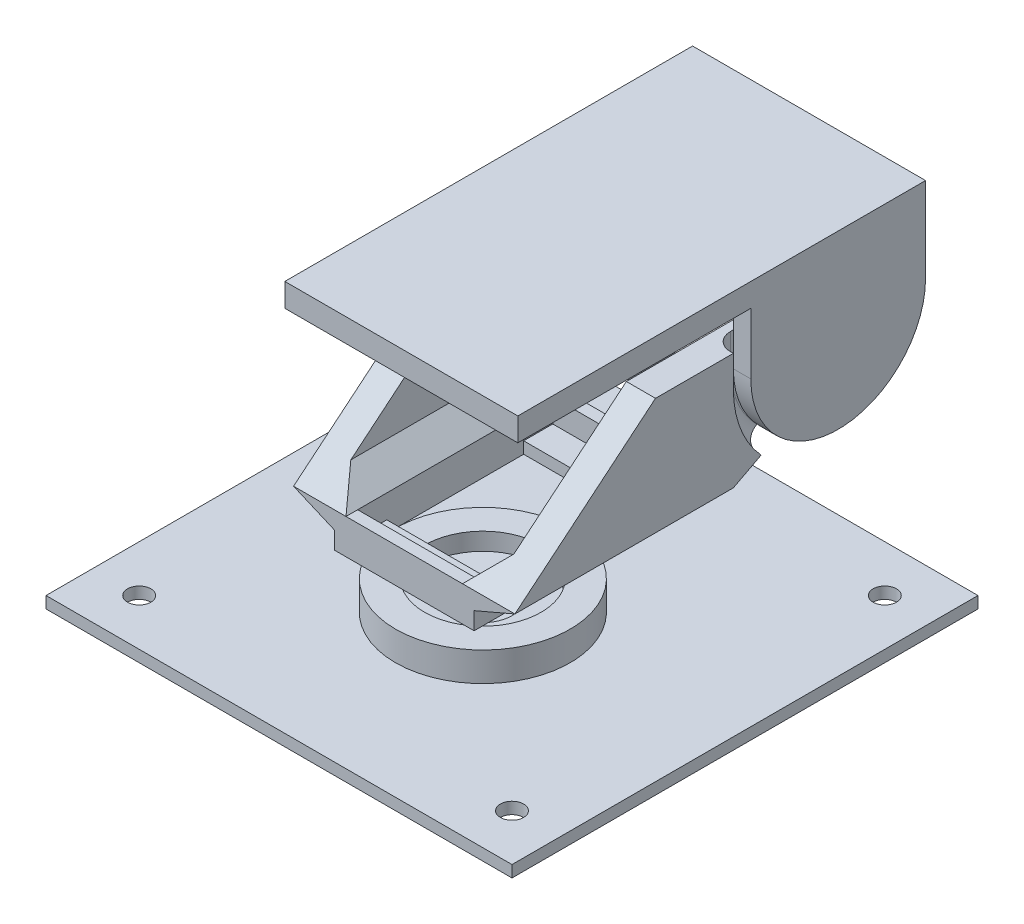
SolidWorks part; units mm, degrees
note: The reader was unsure of these and kept them because the rebuilt part matched: shared geometry of "Sketch9<3>".
other "TiltMount"
other "Base"
other "PanMount"
other "Pin_outer"
other "Pin_inner"
ref_plane "Front Plane" through (0, 0, 0) normal (0, 0, 1) x (1, 0, 0)
ref_plane "Top Plane" through (0, 0, 0) normal (0, 1, 0) x (1, 0, 0)
ref_plane "Right Plane" through (0, 0, 0) normal (1, 0, 0) x (0, 0, -1)
sketch "Sketch1" plane through (0, 0, 0) normal (0, 1, 0) x (1, 0, 0)
  line L1 (-40, -40) -> (40, -40)
  line L2 (-40, -40) -> (-40, 40)
  line L3 (-40, 40) -> (40, 40)
  line L4 (40, -40) -> (40, 40)
  line L5 (-40, -40) -> (40, 40) construction
  line L6 (-40, 40) -> (40, -40) construction
  point P0 (0, 0)
  dimension "D1" = 80
  dimension "D2" = 80
extrude "Boss-Extrude1" add sketch "Sketch1" along normal blind 2
sketch "Sketch2" plane through (0, 2, 0) normal (0, 1, 0) x (1, 0, 0)
  line L0 (0, 0) -> (0, -5) construction
  circle A0 centre (0, -5) radius 5
  circle A1 centre (0, -5) radius 15
  dimension "D1" = 10
  dimension "D3" = 30
  dimension "D2" = 5
extrude "Boss-Extrude2" add sketch "Sketch2" along normal blind 5
sketch "Sketch14" plane through (0, 2, 0) normal (0, 1, 0) x (1, 0, 0)
  line L8 (32, -32) -> (32, 32)
  line L9 (32, 32) -> (-32, 32)
  line L10 (-32, 32) -> (-32, -32)
  line L11 (-32, -32) -> (32, -32)
  line L12 (32, -32) -> (32, 32) construction
  line L13 (32, 32) -> (-32, 32) construction
  line L14 (-32, 32) -> (-32, -32) construction
  line L15 (-32, -32) -> (32, -32) construction
  circle A0 centre (-32, 32) radius 2
  circle A1 centre (32, 32) radius 2
  circle A2 centre (32, -32) radius 2
  circle A3 centre (-32, -32) radius 2
  dimension "D2" = 4
  dimension "D1" = 8
sketch "Sketch13" plane through (0, 7, 0) normal (0, 1, 0) x (1, 0, 0)
  circle A0 centre (0, -5) radius 10
  dimension "D1" = 20
extrude "Cut-Extrude1" cut sketch "Sketch13" against normal offset from surface (3 mm away) 2 up to face at (0, 2, 20)
sketch "Sketch4" plane through (0, 2, 0) normal (0, 1, 0) x (1, 0, 0)
  line L0 (0, 0) -> (0, 17) construction
  line L1 (-12, 19) -> (12, 19)
  line L2 (-12, 19) -> (-12, -18.5)
  line L3 (-12, -18.5) -> (12, -18.5)
  line L4 (12, 19) -> (12, -18.5)
  line L5 (-10, 17) -> (-10, -16.5)
  line L6 (-10, -16.5) -> (10, -16.5)
  line L7 (10, 17) -> (10, -16.5)
  line L8 (-10, 17) -> (10, 17)
  dimension "D1" = 33.5
  dimension "D2" = 24
  dimension "D3" = 17
  dimension "D4" = 2
extrude "Boss-Extrude3" add sketch "Sketch4" along normal blind 6 from offset 10
sketch "Sketch5" plane through (-12, 0, 0) normal (-1, 0, 0) x (0, 0, 1)
  line L0 (-42, 38) -> (-5.6333, 38)
  line L1 (-5.6333, 38) -> (18.5, 18)
  line L2 (18.5, 18) -> (-19, 18)
  line L3 (-19, 18) -> (-42, 30)
  line L6 (-42, 30) -> (-42, 38)
  line L7 (-42, 32.6957) -> (-37, 32.6957) construction
  line L8 (-37, 32.6957) -> (-37, 38) construction
  line L9 (-37, 32.6957) -> (-37, 27.3913) construction
  line L15 (-19, 18) -> (-19, 12) construction
  circle A0 centre (-37, 32.6957) radius 1.3
  dimension "D2" = 2.6
  dimension "D1" = 20
  dimension "D3" = 8
  dimension "D4" = 5
  dimension "D5" = 18
extrude "Boss-Extrude4" add sketch "Sketch5" along normal blind 5 from offset 2 separate body
sketch "Sketch6" plane through (0, 0, 18.5) normal (0, 0, 1) x (1, 0, 0)
  line L0 (-19, 18) -> (-12, 15)
  line L1 (-12, 18) -> (-12, 12) construction
  line L2 (-12, 15) -> (-12, 18)
  line L3 (-14, 18) -> (-19, 18)
  line L4 (-14, 22) -> (-10, 18)
  line L5 (-14, 18) -> (-14, 38) construction
  line L6 (-12, 18) -> (12, 18) construction
  line L7 (-10, 18) -> (-12, 18)
  line L8 (-14, 18) -> (-14, 22)
  dimension "D1" = 4
extrude "Boss-Extrude5" add sketch "Sketch6" against normal up to surface (45.1667 mm away) up to face at (-16.5, 24, -30.5)
sketch "Sketch10" plane through (0, 12, 0) normal (0, -1, 0) x (1, 0, 0)
  line L0 (10, 16.5) -> (10, -17) construction
  line L1 (-10, 16.5) -> (10, 16.5)
  line L2 (-10, 16.5) -> (-10, 11.5)
  line L3 (-10, 11.5) -> (10, 11.5)
  line L4 (10, 16.5) -> (10, 11.5)
  line L5 (-10, -17) -> (-10, 16.5) construction
  line L6 (10, -17) -> (-10, -17)
  line L7 (10, -17) -> (10, -12)
  line L8 (10, -12) -> (-10, -12)
  line L9 (-10, -17) -> (-10, -12)
  dimension "D1" = 5
extrude "Boss-Extrude8" add sketch "Sketch10" against normal blind 2
sketch "Sketch20" plane through (-14, 0, 0) normal (-1, 0, 0) x (0, 0, 1)
  line L0 (18.5, 18) -> (13.6733, 22) construction
  line L1 (18.5, 18) -> (13.6733, 22)
  line L2 (13.6733, 22) -> (18.5, 22)
  line L3 (18.5, 22) -> (18.5, 18)
extrude "Cut-Extrude3" cut sketch "Sketch20" against normal blind 10
mirror "Mirror2" about plane through (0, 0, 0) normal (1, 0, 0) of bodies 131 105
sketch "Sketch9" plane through (-19, 0, 0) normal (1, 0, 0) x (0, 0, -1)
  line L0 (42, 43.1957) -> (38.9267, 32.1591)
  line L2 (32, 43.1957) -> (35.0733, 32.1591)
  line L3 (32, 43.1957) -> (42, 43.1957)
  line L4 (37, 32.6957) -> (37, 43.1957) construction
  arc A0 (35.0733, 32.1591) -> (38.9267, 32.1591) centre (37, 32.6957) ccw
  circle A1 centre (37, 32.6957) radius 1.3
  circle A3 centre (37, 32.6957) radius 1.3 construction
  point P16 (37, 43.1957)
  dimension "D1" = 2
  dimension "D2" = 10.5
  dimension "D3" = 10
extrude "Boss-Extrude7" add sketch "Sketch9" against normal blind 2 separate body
extrude "Cut-Extrude2" cut sketch "Sketch14" against normal blind 2
extrude "Boss-Extrude11" add sketch "Sketch9<3>" along normal blind 2 from offset 33 separate body
sketch "Sketch9<3>" plane through (-19, 0, 0) normal (1, 0, 0) x (0, 0, -1) same geometry as "Sketch9"
sketch "Sketch7" plane through (0, 38, 0) normal (0, 1, 0) x (1, 0, 0)
  line L0 (0, 0) -> (0, 1.5) construction
  line L1 (-21, 52) -> (19, 52)
  line L2 (-21, 52) -> (-21, -18)
  line L3 (-21, -18) -> (19, -18)
  line L4 (19, 52) -> (19, -18)
  line L6 (-21, 42) -> (-21, 32) construction
  line L7 (-19, 42) -> (-14, 42) construction
  line L8 (19, 5.6333) -> (19, 42) construction
  dimension "D1" = 10
  dimension "D3" = 70
extrude "Boss-Extrude6" add sketch "Sketch7" along normal blind 4 from surface at 5.1957 starting at face at (-20, 43.1957, -37)
sketch "Sketch12" plane through (-14, 0, 0) normal (1, 0, 0) x (0, 0, -1)
  line L3 (15.5, 26.6729) -> (20, 26.6729)
  line L5 (52, 43.1957) -> (-18, 43.1957) construction
  line L8 (48, 26.6729) -> (43.5, 26.6729)
  line L10 (48, 26.6729) -> (52, 43.1957)
  line L11 (52, 47.1957) -> (52, 43.1957) construction
  line L12 (52, 43.1957) -> (-18, 43.1957) construction
  line L13 (52, 43.1957) -> (47.5, 43.1957)
  line L14 (15.5, 26.6729) -> (11.5, 43.1957)
  line L15 (11.5, 43.1957) -> (16, 43.1957)
  line L17 (47.5, 43.1957) -> (43.5, 34.6957)
  line L18 (43.5, 34.6957) -> (43.5, 26.6729)
  line L19 (16, 43.1957) -> (20, 34.6957)
  line L20 (20, 34.6957) -> (20, 26.6729)
  point P6 (20.4457, 26.6729)
  point P9 (0, 0)
  dimension "D1" = 6.5
  dimension "D2" = 4.5
  dimension "D3" = 17
  dimension "D4" = 17
  dimension "D5" = 4.5
  dimension "D6" = 2
extrude "Boss-Extrude12" add sketch "Sketch12" against normal blind 3 from offset 22
ref_plane "Plane2" through (0, 39.9046, -11.1121) normal (0, 0.9633, -0.2683) x (1, 0, 0)
ref_plane "Plane1" through (0, 0, 0) normal (-1, 0, 0) x (0, -1, 0)
sketch "Sketch19" plane through (0, 39.9046, -11.1121) normal (0, 0.9633, -0.2683) x (1, 0, 0)
  line L0 (-21, 25.5729) -> (-21, 25.3729)
  line L1 (-21, 26.8729) -> (-21.5, 26.8729)
  line L2 (-21, 28.1729) -> (-21, 25.5729) construction
  line L3 (-21, 25.5729) -> (-14, 25.5729)
  line L4 (-21.5, 28.9194) -> (-21.5, 24.8264) construction
  line L5 (-14, 25.5729) -> (-14, 26.8729) construction
  line L6 (-14, 26.8729) -> (-21, 26.8729) construction
  line L7 (-21, 28.1729) -> (-21, 25.5729) construction
  line L8 (-14, 26.2229) -> (-20.5, 26.2229)
  line L9 (-20.5, 26.2229) -> (-20.5, 26.8729)
  line L10 (-20.5, 26.8729) -> (-21, 26.8729)
  line L11 (-14, 26.2229) -> (-14, 25.5729)
  line L12 (-14, 19.7875) -> (-14, -19.0739) construction
  line L13 (-21.5, 26.8729) -> (-21.5, 25.3729)
  line L14 (-21.5, 25.3729) -> (-21, 25.3729)
  point P8 (-21.5, 26.8729)
  dimension "D1" = 0.5
  dimension "D2" = 1.5
  dimension "D4" = 0.5
revolve "Revolve1" add sketch "Sketch19" angle 360 about L6
sketch "Sketch23" plane through (0, 39.9046, -11.1121) normal (0, 0.9633, -0.2683) x (1, 0, 0)
  line L0 (-20.5, 26.8729) -> (-14, 26.8729)
  line L1 (-21, 26.8729) -> (-19, 26.8729) construction
  line L3 (-14, -4.7671) -> (-14, 30.2667) construction
  line L4 (-13, 26.8729) -> (-13, 24.9826) construction
  line L5 (-20.5, 26.2229) -> (-20.5, 27.5229) construction
  line L6 (-14, 27.5229) -> (-14, 28.3729)
  line L7 (-20.5, 26.8729) -> (-20.5, 27.5229)
  line L8 (-21, 28.3729) -> (-14, 28.3729) construction
  line L9 (-14, 26.8729) -> (-13, 26.8729)
  line L10 (-20.5, 27.5229) -> (-14, 27.5229)
  line L11 (-14, 26.2229) -> (-14, 27.5229) construction
  line L12 (-13, 26.8729) -> (-13, 28.3729)
  line L13 (-13, 28.3729) -> (-14, 28.3729)
  line L14 (-21, -30.001) -> (-21, 37.4333) construction
  line L15 (-21, 28.3729) -> (-21.5, 28.3729) construction
  dimension "D1" = 1
revolve "Revolve2" add sketch "Sketch23" angle 360 about L0
delete or keep bodies "Body-Delete/Keep 2" type delete bodies bodies 122
sketch "Sketch25" plane through (19, 0, 0) normal (1, 0, 0) x (0, 0, -1)
  line L0 (22, 32.6957) -> (22, 43.1957)
  line L1 (52, 43.1957) -> (-18, 43.1957) construction
  line L2 (52, 32.6957) -> (52, 43.1957)
  line L3 (22, 43.1957) -> (52, 43.1957)
  arc A0 (22, 32.6957) -> (52, 32.6957) centre (37, 32.6957) ccw
  dimension "D1" = 15
extrude "Boss-Extrude13" add sketch "Sketch25" against normal blind 3
sketch "Sketch26" plane through (19, 0, 0) normal (1, 0, 0) x (0, 0, -1)
  line L10 (-21, 40.1957) -> (19, 40.1957)
  line L11 (19, 40.1957) -> (19, 32.6957)
  line L12 (55, 32.6957) -> (55, 50.1957)
  line L13 (55, 50.1957) -> (-21, 50.1957)
  line L14 (-21, 50.1957) -> (-21, 40.1957)
  line L15 (-21, 40.1957) -> (19, 40.1957)
  line L17 (55, 32.6957) -> (55, 50.1957)
  line L18 (55, 50.1957) -> (-21, 50.1957)
  line L19 (-21, 50.1957) -> (-21, 40.1957)
  line L20 (19, 40.1957) -> (19, 32.6957)
  arc A2 (19, 32.6957) -> (55, 32.6957) centre (37, 32.6957) ccw
  arc A4 (19, 32.6957) -> (55, 32.6957) centre (37, 32.6957) ccw
  dimension "D1" = 3
extrude "Cut-Extrude4" cut sketch "Sketch26" against normal offset from surface (3.5 mm away) 1.5 up to face at (14, 30, -20.5253)
other "Save Bodies1"
fillet "Fillet1" radius 3 2 edges at (15.5, 26.1428, -20.2351) (15.5, 35.3478, -19)
